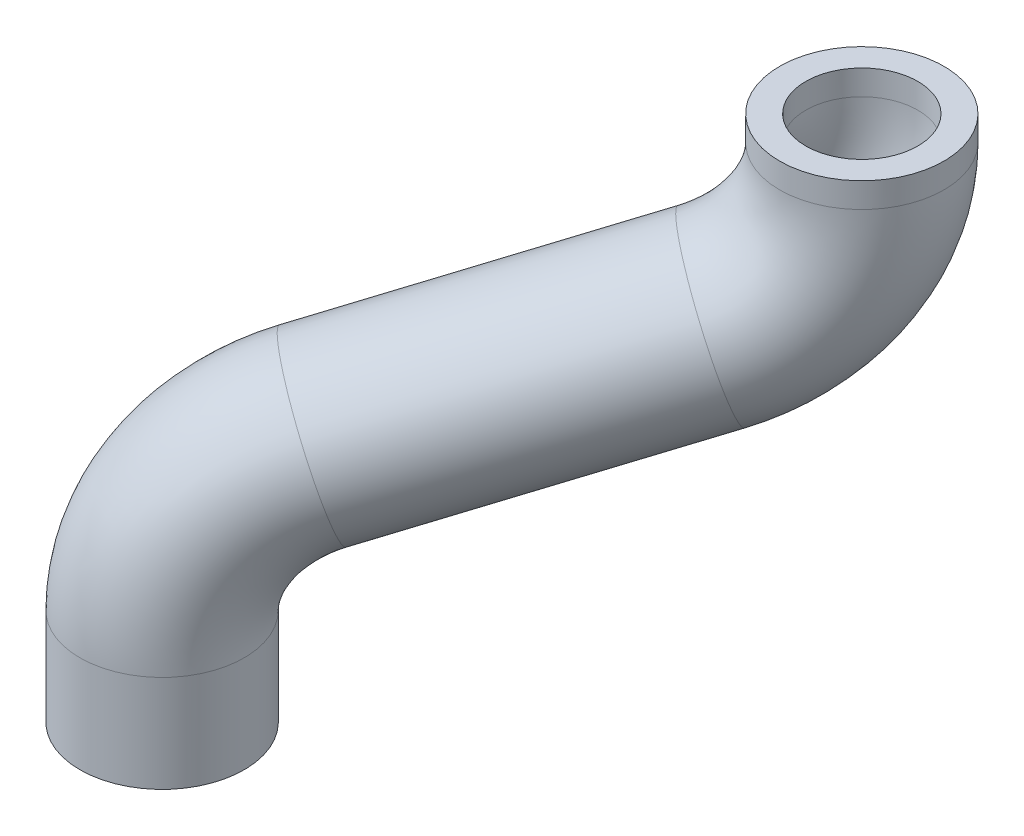
SolidWorks part; units mm, degrees
material "ABS PC"
ref_plane "Front" through (0, 0, 0) normal (0, 0, 1) x (1, 0, 0)
ref_plane "Top" through (0, 0, 0) normal (0, 1, 0) x (1, 0, 0)
ref_plane "Right" through (0, 0, 0) normal (1, 0, 0) x (0, 0, -1)
ref_axis "Axis1" through (0, 0, 55) along (0, 0, -1)
sketch3d "3DSketch1"
  line L0 (-278.8086, 47.6945, 105.8858) -> (-278.8086, 60.6776, 105.8858)
  line L1 (-235.6645, 114.5692, 55.3551) -> (-235.6645, 111.2314, 55.3551)
  line L2 (-269.523, 80.0854, 95.0105) -> (-244.95, 91.8235, 66.2304)
  arc A0 (-278.8086, 60.6776, 105.8858) -> (-269.523, 80.0854, 95.0105) centre (-265.6141, 60.6776, 90.4324) ccw
  arc A1 (-244.95, 91.8235, 66.2304) -> (-235.6645, 111.2314, 55.3551) centre (-248.8589, 111.2314, 70.8085) ccw
  point P6 (-281.0676, 60.6776, 77.2379)
  point P9 (-233.4055, 111.2314, 84.003)
ref_plane "Plane1" through (-278.8086, 47.6945, 105.8858) normal (0, 1, 0) x (1, 0, 0)
sketch "Sketch1" plane through (-278.8086, 47.6945, 105.8858) normal (0, 1, 0) x (1, 0, 0)
  circle A0 centre (0, 0) radius 11
  circle A1 centre (0, 0) radius 7.5
  dimension "D1" = 15
  dimension "D2" = 22
sweep "Sweep1" add profiles "Sketch1" path "3DSketch1"
